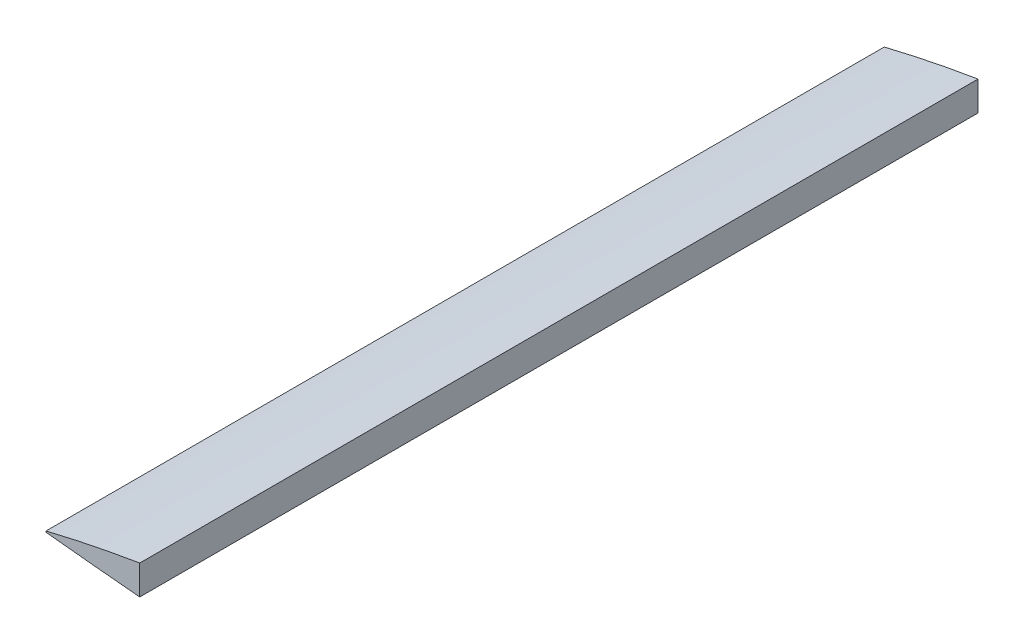
SolidWorks part; units mm, degrees
ref_plane "Front Plane" through (0, 0, 0) normal (0, 0, 1) x (1, 0, 0)
ref_plane "Top Plane" through (0, 0, 0) normal (0, 1, 0) x (1, 0, 0)
ref_plane "Right Plane" through (0, 0, 0) normal (1, 0, 0) x (0, 0, -1)
sketch "Sketch1" plane through (0, 0, 0) normal (0, 0, 1) x (1, 0, 0)
  line L0 (-194.7821, 14.3623) -> (-194.7821, -7.1181)
  line L1 (-263.219, 0.4204) -> (-263.219, -0.4137)
  spline S0 degree 3 poles (-194.7821, 14.3623) (-196.7808, 14.0308) (-201.6443, 13.2242) (-209.199, 11.8784) (-217.2748, 10.3785) (-224.8169, 8.9105) (-231.7807, 7.4997) (-238.1249, 6.1663) (-243.8123, 4.9313) (-248.8094, 3.8144) (-253.0872, 2.8341) (-256.6212, 2.0071) (-259.3909, 1.3478) (-261.3806, 0.8681) (-262.5698, 0.579) (-263.0945, 0.4508) (-263.219, 0.4204) knots 0 0 0 0 0.087007 0.211705 0.329527 0.439741 0.541661 0.634652 0.718135 0.791585 0.85454 0.906603 0.947445 0.976805 0.994497 1 1 1 1
  spline S1 degree 3 poles (-194.7821, -7.1181) (-196.5127, -6.9612) (-201.1128, -6.5442) (-208.4251, -5.8647) (-216.5467, -5.0997) (-224.1497, -4.3712) (-231.1857, -3.6866) (-237.6098, -3.0518) (-243.3806, -2.4732) (-248.4606, -1.956) (-252.817, -1.5081) (-256.4209, -1.1292) (-259.2495, -0.8392) (-261.2822, -0.6051) (-262.5095, -0.5063) (-263.063, -0.4131) (-263.2098, -0.4136) (-263.219, -0.4137) knots 0 0 0 0 0.075811 0.201508 0.320388 0.431695 0.534719 0.628797 0.713321 0.78774 0.851567 0.90438 0.945827 0.975633 0.993597 0.999599 1 1 1 1
extrude "Boss-Extrude1" add sketch "Sketch1" against normal blind 612
ref_plane "Plane1" through (0, 0, -96.9) normal (0, 0, 1) x (1, 0, 0)
sketch "Sketch2" plane through (0, 0, -96.9) normal (0, 0, 1) x (1, 0, 0)
  line L0 (-217.915, -7.698) -> (-196.915, -7.698)
  line L1 (-196.915, -7.698) -> (-196.915, 3.802)
  line L2 (-196.915, 3.802) -> (-217.915, 3.802)
  line L3 (-217.915, 3.802) -> (-217.915, -7.698)
extrude "Cut-Extrude1" cut sketch "Sketch2" along normal blind 13
